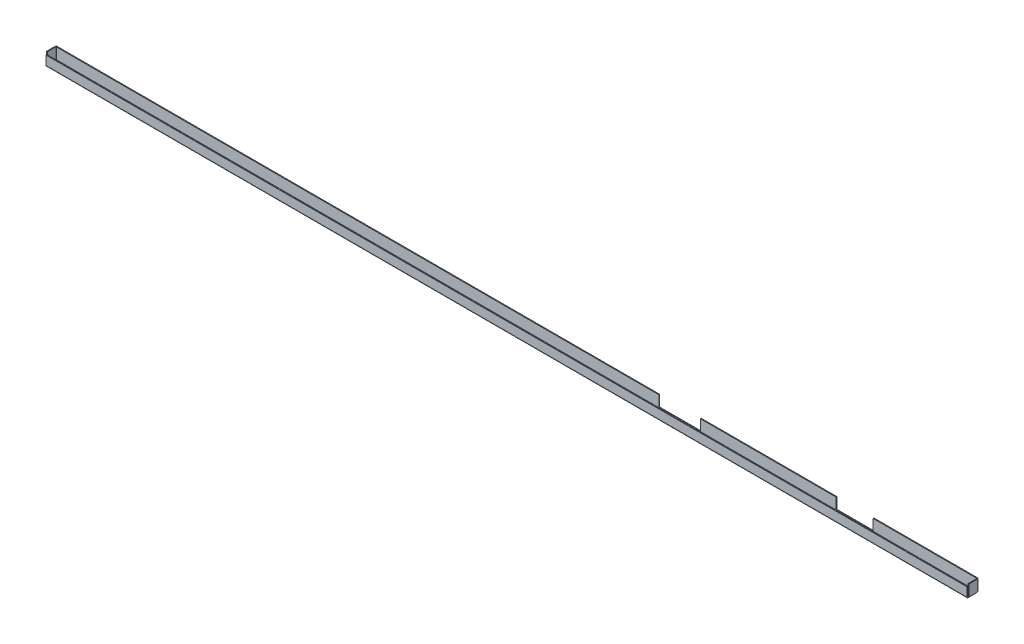
SolidWorks part; units mm, degrees
note: The reader was unsure of these and kept them because the rebuilt part matched: flange length of "边线-法兰1", "边线-法兰2", "边线-法兰3".
ref_plane "前视基准面" through (0, 0, 0) normal (0, 0, 1) x (1, 0, 0)
ref_plane "上视基准面" through (0, 0, 0) normal (0, 1, 0) x (1, 0, 0)
ref_plane "右视基准面" through (0, 0, 0) normal (1, 0, 0) x (0, 0, -1)
other "Configuration Table"
sketch "草图1" plane through (0, 0, 0) normal (0, 0, 1) x (1, 0, 0)
  line L0 (-2034, 18) -> (-66, 18) construction
  line L1 (-2102, 18) -> (2, 18)
  line L2 (-2102, 18) -> (-2102, -3)
  line L3 (-2102, -3) -> (2, -3)
  line L4 (2, 18) -> (2, -3)
  line L5 (0, 210) -> (0, 0) construction
  line L6 (-2100, 0) -> (-2100, 210) construction
  dimension "D1" = 21
  dimension "D2" = 2
  dimension "D3" = 2
base flange "基体-法兰1" sketch "草图1" thickness 2 reverse thickness direction yes parameters "D1"=0.7366
edge flange "边线-法兰1" sketch "草图8" flange angle 90 flange length 21 flange position material outside bend radius 0.7366 thickness 2 relief rectangular parameters "D6"=10
sketch "草图8" plane through (0, -3, 0) normal (0, 1, 0) x (1, 0, 0)
  line L2 (-2102, 0) -> (-2102, 21)
  line L3 (-2102, 21) -> (2, 21)
  line L4 (2, 21) -> (2, 0)
  line L5 (2, 0) -> (-2102, 0) construction
  line L6 (2, 0) -> (-2102, 0)
bend "边线折弯1" bend radius 0.7366 bend angle 90 parameters "D5"=1
edge flange "边线-法兰2" sketch "草图11" flange angle 90 flange length 26 flange position material outside bend radius 0.7366 thickness 2 relief rectangular parameters "D6"=10
sketch "草图11" plane through (0, -3, -21) normal (0, 0, 1) x (1, 0, 0)
  line L2 (-2102, 0) -> (-2102, 26)
  line L3 (-2102, 26) -> (2, 26)
  line L4 (2, 26) -> (2, 0)
  line L5 (2, 0) -> (-2102, 0) construction
  line L6 (2, 0) -> (-2102, 0)
bend "边线折弯2" bend radius 0.7366 bend angle 90 parameters "D5"=2
edge flange "边线-法兰3" sketch "草图16" flange profiles "草图16", "草图17" flange angle 90 flange length 20 flange position material outside bend radius 0.7366 thickness 2 relief none parameters "D6"=10, "D8"=1
sketch "草图16" plane through (2, 0, -21) normal (-1, 0, 0) x (0, -1, 0)
  line L2 (-23, 0) -> (-23, 20)
  line L3 (-23, 20) -> (2.2634, 20)
  line L4 (2.2634, 20) -> (2.2634, 0)
  line L5 (2.2634, 0) -> (-23, 0) construction
  line L6 (2.2634, 0) -> (-23, 0)
sketch "草图17" plane through (-2102, 0, -21) normal (1, 0, 0) x (0, 1, 0)
  line L0 (23, 0) -> (-2.2634, 0) construction
  line L1 (23, 0) -> (-2.2634, 0)
  line L2 (23, 0) -> (23, 20)
  line L3 (23, 20) -> (-2.2634, 20)
  line L4 (-2.2634, 20) -> (-2.2634, 0)
bend "边线折弯3" bend radius 0.7366 bend angle 90 parameters "D5"=3
bend "边线折弯4" bend radius 0.7366 bend angle 90 parameters "D5"=4
sketch "草图18" plane through (0, 0, -23) normal (0, 0, -1) x (-1, 0, 0)
  line L0 (-1.2634, -2.2634) -> (2101.2634, -2.2634) construction
  line L1 (235, -2.2634) -> (320, -2.2634)
  line L2 (235, -2.2634) -> (235, 36.9707)
  line L3 (235, 36.9707) -> (320, 36.9707)
  line L4 (320, -2.2634) -> (320, 36.9707)
  line L5 (240, 30) -> (240, 0) construction
  line L6 (630, -2.2634) -> (725, -2.2634)
  line L7 (630, -2.2634) -> (630, 40.0452)
  line L8 (630, 40.0452) -> (725, 40.0452)
  line L9 (725, -2.2634) -> (725, 40.0452)
  line L10 (315, 0) -> (315, 30) construction
  line L11 (635, 30) -> (635, 0) construction
  line L12 (720, 0) -> (720, 30) construction
  dimension "D1" = 5
  dimension "D2" = 5
  dimension "D3" = 5
  dimension "D4" = 5
extrude "切除-拉伸1" cut sketch "草图18" against normal blind 2 normal cut yes
sketch "草图19" plane through (0, 0, -23) normal (0, 0, -1) x (-1, 0, 0)
  line L0 (-1.2634, 10.3683) -> (2101.2634, 10.3683) construction
  line L1 (-1.2634, 23) -> (-1.2634, -2.2634) construction
  line L2 (2101.2634, -2.2634) -> (2101.2634, 23) construction
  circle A0 centre (98.7366, 10.3683) radius 6
  circle A1 centre (98.7366, 199.6317) radius 6 construction
  circle A2 centre (478.7366, 10.3683) radius 6
  circle A3 centre (858.7366, 10.3683) radius 6
  circle A4 centre (1238.7366, 10.3683) radius 6
  circle A5 centre (1618.7366, 10.3683) radius 6
  circle A6 centre (1998.7366, 10.3683) radius 6
  dimension "D1" = 12
  dimension "D2" = 0
  dimension "D3" = 6
extrude "切除-拉伸2" cut sketch "草图19" against normal blind 0.1 normal cut yes
sketch "折弯-线1" plane through (0, 0, 0) normal (0, 1, 0) x (1, 0, 0)
sketch "边界框1" plane through (0, 0, 0) normal (0, 1, 0) x (1, 0, 0)
sheet metal parameters "钣金6" thickness 2 parameters "D1"=0.7366
flat pattern "平板型式6" [suppressed]
sketch "折弯-线2" plane through (0, 0, 0) normal (0, 1, 0) x (1, 0, 0)
sketch "边界框2" [suppressed] plane through (0, 0, 0) normal (0, 1, 0) x (1, 0, 0)
sheet metal parameters "钣金7" thickness 2 parameters "D1"=0.7366
flat pattern "平板型式6" [suppressed]
sketch "折弯-线2" plane through (0, 0, 0) normal (0, 1, 0) x (1, 0, 0)
sketch "边界框2" [suppressed] plane through (0, 0, 0) normal (0, 1, 0) x (1, 0, 0)
bend of the flat pattern "展平-<边线折弯1>1"
sheet metal parameters "钣金8" thickness 2 parameters "D1"=0.7366
flat pattern "平板型式6" [suppressed]
sketch "折弯-线2" plane through (0, 0, 0) normal (0, 1, 0) x (1, 0, 0)
sketch "边界框2" [suppressed] plane through (0, 0, 0) normal (0, 1, 0) x (1, 0, 0)
bend of the flat pattern "展平-<边线折弯1>1"
bend of the flat pattern "展平-<边线折弯2>1"
sheet metal parameters "钣金9" thickness 2 parameters "D1"=0.7366
flat pattern "平板型式6" [suppressed]
sketch "折弯-线2" plane through (0, 0, 0) normal (0, 1, 0) x (1, 0, 0)
sketch "边界框2" [suppressed] plane through (0, 0, 0) normal (0, 1, 0) x (1, 0, 0)
bend of the flat pattern "展平-<边线折弯1>1"
bend of the flat pattern "展平-<边线折弯2>1"
bend of the flat pattern "展平-<边线折弯3>1"
bend of the flat pattern "展平-<边线折弯4>1"
sheet metal parameters "钣金10" thickness 2 parameters "D1"=0.7366
flat pattern "平板型式6" [suppressed]
sketch "折弯-线2" plane through (0, 0, 0) normal (0, 1, 0) x (1, 0, 0)
sketch "边界框2" [suppressed] plane through (0, 0, 0) normal (0, 1, 0) x (1, 0, 0)
bend of the flat pattern "展平-<边线折弯1>1"
bend of the flat pattern "展平-<边线折弯2>1"
bend of the flat pattern "展平-<边线折弯3>1"
bend of the flat pattern "展平-<边线折弯4>1"
sheet metal parameters "钣金11" thickness 2 parameters "D1"=0.7366
flat pattern "平板型式6" [suppressed]
sketch "折弯-线2" plane through (0, 0, 0) normal (0, 1, 0) x (1, 0, 0)
sketch "边界框2" [suppressed] plane through (0, 0, 0) normal (0, 1, 0) x (1, 0, 0)
bend of the flat pattern "展平-<边线折弯1>1"
bend of the flat pattern "展平-<边线折弯2>1"
bend of the flat pattern "展平-<边线折弯3>1"
bend of the flat pattern "展平-<边线折弯4>1"
